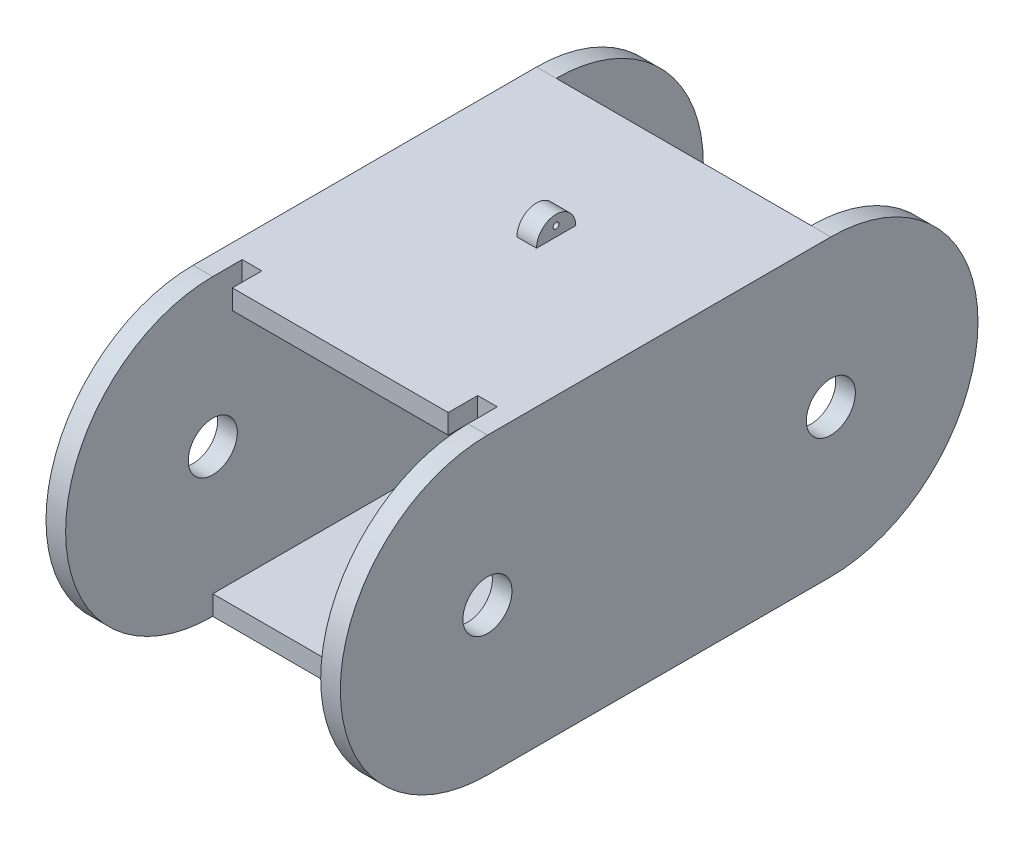
SolidWorks part; units mm, degrees
ref_plane "Front Plane" through (0, 0, 0) normal (0, 0, 1) x (1, 0, 0)
ref_plane "Top Plane" through (0, 0, 0) normal (0, 1, 0) x (1, 0, 0)
ref_plane "Right Plane" through (0, 0, 0) normal (1, 0, 0) x (0, 0, -1)
ref_plane "End Plane" through (0, 0, -31.75) normal (0, 0, 1) x (1, 0, 0)
ref_plane "Inside Plane" through (0, 19.05, 0) normal (0, 1, 0) x (1, 0, 0)
sketch "Sketch1" plane through (0, 0, 0) normal (0, 1, 0) x (1, 0, 0)
  line L1 (0, 0) -> (19.05, 0)
  line L2 (0, 0) -> (0, 41.275)
  line L3 (0, 41.275) -> (19.05, 41.275)
  line L4 (19.05, 0) -> (19.05, 41.275)
  dimension "D1" = 41.275
  dimension "D2" = 19.05
extrude "Boss-Extrude1" add sketch "Sketch1" along normal blind 19.05
sketch "Sketch2" plane through (0, 0, 0) normal (0, 0, 1) x (1, 0, 0)
  line L0 (0, 19.05) -> (19.05, 19.05) construction
  line L1 (1.27, 17.78) -> (17.78, 17.78)
  line L2 (1.27, 17.78) -> (1.27, 1.27)
  line L3 (1.27, 1.27) -> (17.78, 1.27)
  line L4 (17.78, 17.78) -> (17.78, 1.27)
  line L5 (0, 19.05) -> (0, 0) construction
  line L6 (0, 0) -> (19.05, 0) construction
  line L7 (19.05, 19.05) -> (19.05, 0) construction
  dimension "D1" = 1.27
  dimension "D2" = 1.27
  dimension "D3" = 1.27
  dimension "D4" = 1.27
extrude "Cut-Extrude1" cut sketch "Sketch2" against normal blind 50.8
sketch "Sketch3" plane through (0, 19.05, 0) normal (0, 1, 0) x (1, 0, 0)
  line L0 (0, 41.275) -> (0, 0) construction
  line L1 (8.89, 24.13) -> (10.16, 24.13)
  line L2 (8.89, 24.13) -> (8.89, 21.59)
  line L3 (8.89, 21.59) -> (10.16, 21.59)
  line L4 (10.16, 24.13) -> (10.16, 21.59)
  line L5 (0, 0) -> (19.05, 0) construction
  dimension "D1" = 1.27
  dimension "D2" = 8.89
  dimension "D3" = 21.59
  dimension "D4" = 2.54
extrude "Boss-Extrude2" add sketch "Sketch3" along normal blind 1.27
sketch "Sketch4" plane through (0, 0, 0) normal (1, 0, 0) x (0, 0, -1)
  line L0 (24.13, 19.05) -> (21.59, 19.05) construction
  line L1 (22.86, 20.32) -> (22.86, 19.685) construction
  line L2 (41.275, 19.05) -> (0, 19.05) construction
  line L3 (21.59, 20.32) -> (24.13, 20.32) construction
  line L4 (41.275, 0) -> (0, 0) construction
  line L5 (0, 19.05) -> (0, 0) construction
  circle A0 centre (22.86, 19.685) radius 0.1905
  arc A1 (24.13, 19.05) -> (21.59, 19.05) centre (22.86, 20.4483) ccw
  circle A4 centre (9.525, 9.525) radius 1.5875
  arc A6 (9.525, 19.05) -> (9.525, 0) centre (9.525, 9.525) ccw
  arc A7 (9.525, 19.05) -> (9.525, 0) centre (4.0998, 9.525) ccw
  ellipse E0 centre (22.86, 19.05) end of major axis (22.86, 20.32) minor radius 1.27 (24.13, 19.05) -> (21.59, 19.05) ccw
  dimension "D1" = 0.635
  dimension "D4" = 9.525
  dimension "D5" = 9.525
extrude "Cut-Extrude2" cut sketch "Sketch4" along normal blind 19.05
fillet "Fillet1" [suppressed] radius 0.635
fillet "Fillet2" [suppressed] radius 2.54
ref_plane "Mirror Plane" through (0, 0, -20.6375) normal (0, 0, 1) x (1, 0, 0)
mirror "Mirror1" about plane through (0, 0, -20.6375) normal (0, 0, 1) of "Cut-Extrude2"
sketch "Sketch7" plane through (0, 19.05, 0) normal (0, 1, 0) x (1, 0, 0)
  line L0 (2.54, 9.525) -> (16.51, 9.525)
  line L1 (1.27, 0) -> (2.54, 0)
  line L2 (1.27, 0) -> (1.27, 11.43)
  line L3 (1.27, 11.43) -> (2.54, 11.43)
  line L4 (2.54, 9.525) -> (2.54, 11.43)
  line L5 (17.78, 0) -> (16.51, 0)
  line L6 (17.78, 0) -> (17.78, 11.43)
  line L7 (17.78, 11.43) -> (16.51, 11.43)
  line L8 (16.51, 9.525) -> (16.51, 11.43)
  line L9 (19.05, 9.525) -> (0, 9.525) construction
  line L10 (2.54, 0) -> (16.51, 0)
  dimension "D1" = 1.27
  dimension "D2" = 1.27
  dimension "D3" = 11.43
  dimension "D4" = 11.43
extrude "Cut-Extrude3" cut sketch "Sketch7" against normal blind 12.7
sketch "Sketch8" plane through (0, 19.05, 0) normal (0, 1, 0) x (1, 0, 0)
  line L0 (1.27, 0) -> (1.27, 9.525) construction
  line L1 (1.27, 4.0341) -> (17.78, 4.0341)
  line L2 (1.27, 4.0341) -> (1.27, 9.525)
  line L3 (1.27, 9.525) -> (17.78, 9.525)
  line L4 (17.78, 4.0341) -> (17.78, 9.525)
  line L5 (19.05, 31.75) -> (0, 31.75) construction
  line L6 (17.78, 36.5019) -> (1.27, 36.5019)
  line L7 (17.78, 36.5019) -> (17.78, 31.75)
  line L8 (17.78, 31.75) -> (1.27, 31.75)
  line L9 (1.27, 36.5019) -> (1.27, 31.75)
extrude "Cut-Extrude4" cut sketch "Sketch8" against normal blind 25.4
sketch "Sketch9" plane through (0, 0, 0) normal (0, 1, 0) x (1, 0, 0)
  line L0 (1.27, 9.525) -> (17.78, 9.525) construction
  line L1 (12.065, 22.225) -> (8.255, 22.225)
  line L2 (12.065, 22.225) -> (12.065, 27.305)
  line L3 (12.065, 27.305) -> (8.255, 27.305)
  line L4 (8.255, 22.225) -> (8.255, 27.305)
  line L5 (19.05, 9.525) -> (19.05, 31.75) construction
  dimension "D1" = 3.81
  dimension "D2" = 5.08
  dimension "D3" = 12.7
  dimension "D4" = 6.985
extrude "Boss-Extrude3" add sketch "Sketch9" against normal blind 5.08
sketch "Sketch10" plane through (0, 0, 0) normal (1, 0, 0) x (0, 0, -1)
  line L0 (27.305, -5.08) -> (27.305, 0) construction
  line L1 (22.225, -5.08) -> (27.305, -5.08) construction
  line L2 (22.225, -5.08) -> (22.225, 0) construction
  line L3 (22.225, 0) -> (27.305, 0) construction
  line L4 (22.225, -2.54) -> (22.225, 0)
  line L5 (25.1652, 0) -> (27.305, 0)
  line L6 (9.525, 0) -> (31.75, 0) construction
  arc A0 (27.305, -2.54) -> (24.765, -5.08) centre (24.765, -2.54) cw
  arc A1 (24.765, -5.08) -> (22.225, -2.54) centre (24.765, -2.54) cw
  arc A2 (27.305, -2.54) -> (26.0285, -1.3339) centre (26.0637, -2.5752) ccw
  arc A3 (26.0285, -1.3339) -> (26.0483, -2.0347) centre (26.0384, -1.6843) ccw
  arc A4 (26.0483, -2.0347) -> (26.68, -2.5752) centre (26.0422, -2.6811) cw
  arc A5 (26.68, -2.5752) -> (24.765, -4.4612) centre (24.5539, -2.3316) cw
  arc A6 (24.765, -4.4612) -> (22.9012, -2.54) centre (25.0593, -2.311) cw
  arc A7 (22.9012, -2.54) -> (25.1652, 0) centre (27.0171, -3.9296) cw
  arc A8 (27.305, 0) -> (22.225, 0) centre (24.765, -2.8187) cw
extrude "Cut-Extrude5" cut sketch "Sketch10" along normal blind 25.4
